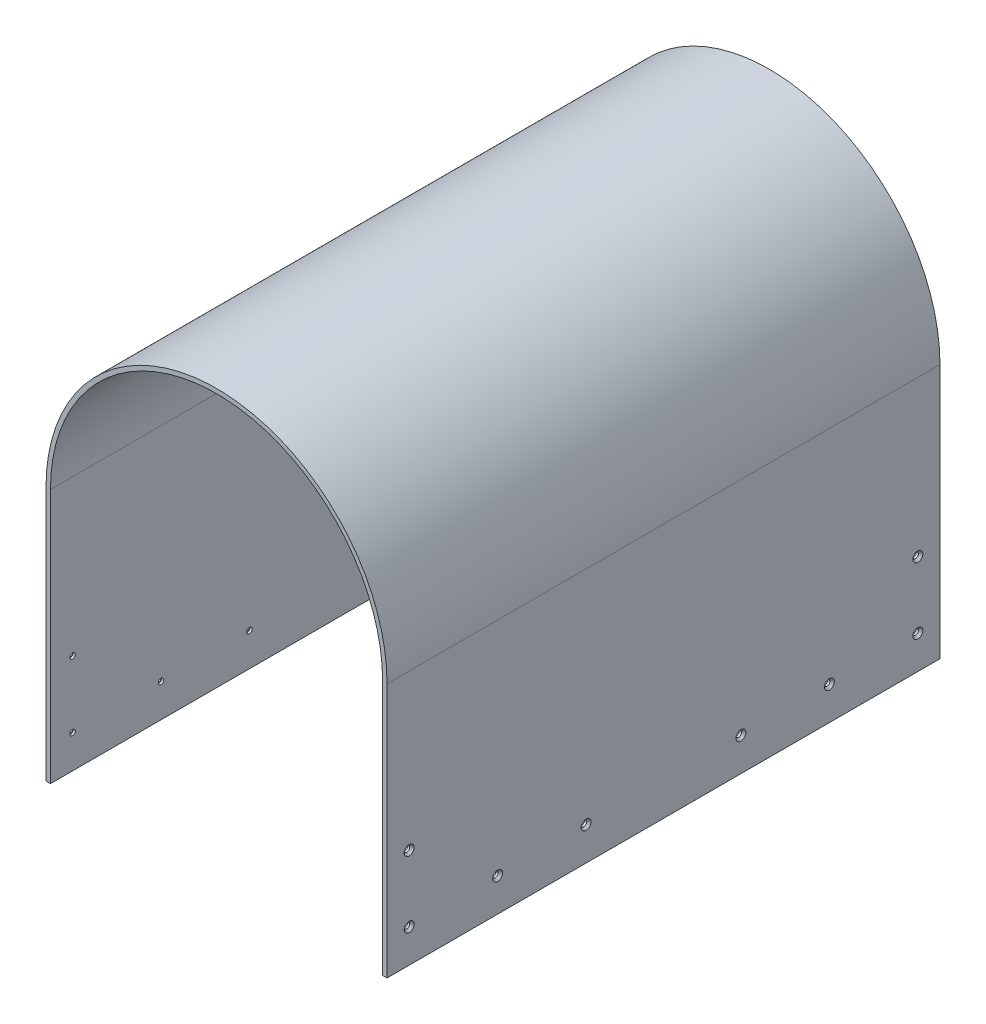
SolidWorks part; units mm, degrees
material "ABS PC"
ref_plane "Front Plane" through (0, 0, 0) normal (0, 0, 1) x (1, 0, 0)
ref_plane "Top Plane" through (0, 0, 0) normal (0, 1, 0) x (1, 0, 0)
ref_plane "Right Plane" through (0, 0, 0) normal (1, 0, 0) x (0, 0, -1)
sketch "Sketch1" plane through (0, 0, 0) normal (0, 0, 1) x (1, 0, 0)
  line L0 (0, 0) -> (0, 212.7728) construction
  line L1 (-75.1, 0) -> (-75.1, 115.2)
  line L2 (75.1, 0) -> (75.1, 115.2)
  line L7 (-26.8281, 0) -> (29.8493, 0) construction
  line L8 (-77.1, 0) -> (-77.1, 115.2)
  line L9 (77.1, 0) -> (77.1, 115.2)
  line L10 (-75.1, 0) -> (-77.1, 0)
  line L11 (75.1, 0) -> (77.1, 0)
  arc A2 (77.1, 115.2) -> (-77.1, 115.2) centre (0, 115.2) ccw
  arc A4 (75.1, 115.2) -> (-75.1, 115.2) centre (0, 115.2) ccw
  dimension "D4" = 75.1
  dimension "D2" = 150.2
  dimension "D3" = 115.2
  dimension "D1" = 2
extrude "Boss-Extrude1" add sketch "Sketch1" along normal mid plane 250
sketch "Sketch3" plane through (-77.1, 0, 0) normal (-1, 0, 0) x (0, 0, 1)
  line L0 (-125, 15) -> (125, 15) construction
  line L1 (-125, 115.2) -> (-125, 0) construction
  line L2 (125, 115.2) -> (125, 0) construction
  line L3 (125, 0) -> (-125, 0) construction
  circle A0 centre (-115, 15) radius 1.25
  circle A1 centre (-75, 15) radius 1.25
  circle A2 centre (-35, 15) radius 1.25
  circle A3 centre (-115, 45) radius 1.25
  dimension "D2" = 2.5
  dimension "D3" = 2.5
  dimension "D4" = 2.5
  dimension "D5" = 2.5
  dimension "D1" = 15
extrude "Cut-Extrude1" cut sketch "Sketch3" against normal through all
mirror "Mirror1" about plane through (0, 0, 0) normal (0, 0, 1) of "Cut-Extrude1"
chamfer "Chamfer1" distance 1 angle 45 8 edges at (-77.1, 15, 113.75) (-77.1, 45, 113.75) (-77.1, 15, 73.75) (-77.1, 15, 33.75) (-77.1, 15, -33.75) (-77.1, 15, -73.75) (-77.1, 15, -113.75) (-77.1, 45, -113.75)
chamfer "Chamfer2" distance 1 angle 45 8 edges at (77.1, 45, -113.75) (77.1, 15, -113.75) (77.1, 15, -73.75) (77.1, 15, -33.75) (77.1, 15, 33.75) (77.1, 15, 73.75) (77.1, 15, 113.75) (77.1, 45, 113.75)
sketch "Sketch4" plane through (-77.1, 0, 0) normal (-1, 0, 0) x (0, 0, 1)
  line L1 (-29, 70) -> (-11, 70)
  line L2 (-29, 70) -> (-29, 84)
  line L3 (-29, 84) -> (-11, 84)
  line L4 (-11, 70) -> (-11, 84)
  line L5 (-29, 70) -> (-11, 84) construction
  line L6 (-29, 84) -> (-11, 70) construction
  point P0 (-20, 77)
extrude "Cut-Extrude2" cut sketch "Sketch4" against normal up to next
